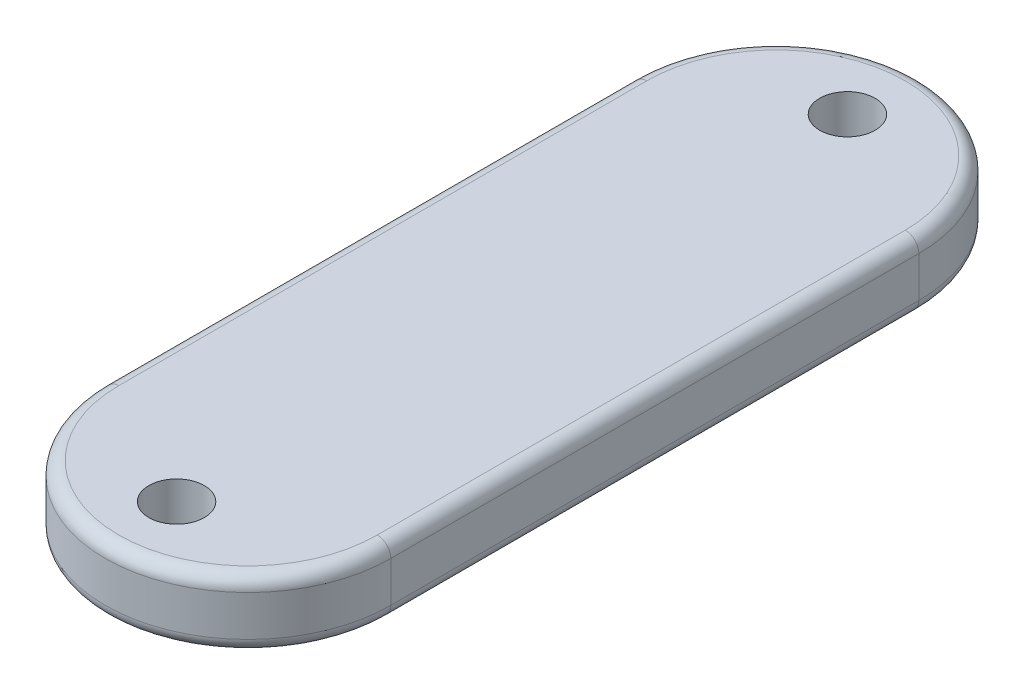
SolidWorks part; units mm, degrees
ref_plane "Plan de face" through (0, 0, 0) normal (0, 0, 1) x (1, 0, 0)
ref_plane "Plan de dessus" through (0, 0, 0) normal (0, 1, 0) x (1, 0, 0)
ref_plane "Plan de droite" through (0, 0, 0) normal (1, 0, 0) x (0, 0, -1)
sketch "Esquisse1" plane through (0, 0, 0) normal (0, 0, 1) x (1, 0, 0)
  line L0 (0, 4) -> (0, 14.517) construction
  line L1 (-2.95, 10.1031) -> (2.95, 10.1031)
  line L22 (2.95, 10.1031) -> (2.95, 8.4831)
  line L23 (2.95, 8.4831) -> (5.71, 8.4831)
  line L24 (5.71, 8.4831) -> (5.71, 6.9831)
  line L25 (5.71, 6.9831) -> (3.5, 4.84)
  line L26 (3.5, 4.84) -> (-3.5, 4.84)
  line L27 (-5.71, 6.9831) -> (-3.5, 4.84)
  line L28 (-5.71, 8.4831) -> (-5.71, 6.9831)
  line L29 (-2.95, 8.4831) -> (-5.71, 8.4831)
  line L30 (-2.95, 10.1031) -> (-2.95, 8.4831)
  point P10 (0, 4.84)
  point P14 (0, 10.1031)
  point P41 (0, 0)
  point P46 (0, 0)
  line B0 (0, 0) -> (0, 4) construction
  line B1 (0, 4) -> (0.866, 4.5)
  line B2 (0, 4) -> (-0.866, 4.5)
  line B3 (0.866, 4.5) -> (3.4393, 4.5)
  line B4 (3.4393, 4.5) -> (6, 7.0607)
  line B5 (6, 7.0607) -> (6, 8.5)
  line B6 (6, 8.5) -> (3, 8.5)
  line B7 (3, 8.5) -> (3, 9.5)
  line B8 (3, 9.5) -> (3.5, 9.5)
  line B9 (3.5, 9.5) -> (3.5, 10)
  line B10 (3.5, 10) -> (8.5, 10)
  line B11 (0, 0) -> (1.2745, 0) construction
  line B12 (-3.5, -10) -> (-8.5, -10)
  line B13 (-3.4393, -4.5) -> (-6, -7.0607)
  line B14 (-3.5, 9.5) -> (-3.5, 10)
  line B15 (-3, 9.5) -> (-3.5, 9.5)
  line B16 (-3, 8.5) -> (-3, 9.5)
  line B17 (-6, 8.5) -> (-3, 8.5)
  line B18 (-6, 7.0607) -> (-6, 8.5)
  line B19 (-0.866, 4.5) -> (-3.4393, 4.5)
  line B20 (-3.4393, 4.5) -> (-6, 7.0607)
  line B21 (-3.5, 10) -> (-8.5, 10)
  line B22 (-0.866, -4.5) -> (-3.4393, -4.5)
  line B23 (-6, -7.0607) -> (-6, -8.5)
  line B24 (-6, -8.5) -> (-3, -8.5)
  line B25 (-3, -8.5) -> (-3, -9.5)
  line B26 (-3, -9.5) -> (-3.5, -9.5)
  line B27 (-3.5, -9.5) -> (-3.5, -10)
  line B28 (3.5, -10) -> (8.5, -10)
  line B29 (3.5, -9.5) -> (3.5, -10)
  line B30 (3, -9.5) -> (3.5, -9.5)
  line B31 (3, -8.5) -> (3, -9.5)
  line B32 (6, -8.5) -> (3, -8.5)
  line B33 (6, -7.0607) -> (6, -8.5)
  line B34 (3.4393, -4.5) -> (6, -7.0607)
  line B35 (0.866, -4.5) -> (3.4393, -4.5)
  line B36 (0, -4) -> (-0.866, -4.5)
  line B37 (0, -4) -> (0.866, -4.5)
  line B38 (10, -3.5) -> (10, -8.5)
  line B39 (9.5, -3.5) -> (10, -3.5)
  line B40 (8.5, -3) -> (9.5, -3)
  line B41 (9.5, -3) -> (9.5, -3.5)
  line B42 (8.5, -6) -> (8.5, -3)
  line B43 (7.0607, -6) -> (8.5, -6)
  line B44 (4.5, -3.4393) -> (7.0607, -6)
  line B45 (4.5, -0.866) -> (4.5, -3.4393)
  line B46 (4.5, 0.866) -> (4.5, 3.4393)
  line B47 (4.5, 3.4393) -> (7.0607, 6)
  line B48 (7.0607, 6) -> (8.5, 6)
  line B49 (8.5, 6) -> (8.5, 3)
  line B50 (8.5, 3) -> (9.5, 3)
  line B51 (9.5, 3) -> (9.5, 3.5)
  line B52 (9.5, 3.5) -> (10, 3.5)
  line B53 (10, 3.5) -> (10, 8.5)
  line B54 (-3.5, -9.5) -> (-3.5, -10)
  line B55 (-3, -8.5) -> (-3, -9.5)
  line B56 (-3, -9.5) -> (-3.5, -9.5)
  line B57 (-6, -8.5) -> (-3, -8.5)
  line B58 (-6, -7.0607) -> (-6, -8.5)
  line B59 (-3.4393, -4.5) -> (-6, -7.0607)
  line B60 (-0.866, -4.5) -> (-3.4393, -4.5)
  line B61 (0.866, -4.5) -> (3.4393, -4.5)
  line B62 (3.4393, -4.5) -> (6, -7.0607)
  line B63 (6, -7.0607) -> (6, -8.5)
  line B64 (6, -8.5) -> (3, -8.5)
  line B65 (3, -8.5) -> (3, -9.5)
  line B66 (3, -9.5) -> (3.5, -9.5)
  line B67 (3.5, -9.5) -> (3.5, -10)
  line B68 (-10, 3.5) -> (-10, 8.5)
  line B69 (-9.5, 3.5) -> (-10, 3.5)
  line B70 (-8.5, 3) -> (-9.5, 3)
  line B71 (-9.5, 3) -> (-9.5, 3.5)
  line B72 (-8.5, 6) -> (-8.5, 3)
  line B73 (-7.0607, 6) -> (-8.5, 6)
  line B74 (-4.5, 3.4393) -> (-7.0607, 6)
  line B75 (-4.5, 0.866) -> (-4.5, 3.4393)
  line B76 (-4.5, -0.866) -> (-4.5, -3.4393)
  line B77 (-4.5, -3.4393) -> (-7.0607, -6)
  line B78 (-7.0607, -6) -> (-8.5, -6)
  line B79 (-8.5, -6) -> (-8.5, -3)
  line B80 (-8.5, -3) -> (-9.5, -3)
  line B81 (-9.5, -3) -> (-9.5, -3.5)
  line B82 (-9.5, -3.5) -> (-10, -3.5)
  line B83 (-10, -3.5) -> (-10, -8.5)
  line B84 (4, 0) -> (4.5, -0.866)
  line B85 (4, 0) -> (4.5, 0.866)
  line B86 (0, -4) -> (-0.866, -4.5)
  line B87 (0, -4) -> (0.866, -4.5)
  line B88 (-4, 0) -> (-4.5, 0.866)
  line B89 (-4, 0) -> (-4.5, -0.866)
  line B90 (0, 0) -> (1.9445, 1.9445) construction
  arc B91 (8.5, 10) -> (10, 8.5) centre (8.5, 8.5) cw
  arc B92 (-8.5, 10) -> (-10, 8.5) centre (-8.5, 8.5) ccw
  arc B93 (-8.5, -10) -> (-10, -8.5) centre (-8.5, -8.5) cw
  arc B94 (8.5, -10) -> (10, -8.5) centre (8.5, -8.5) ccw
  circle B95 centre (0, 0) radius 2.75
  dimension "D1" = 2.95
  dimension "D2" = 1.62
  dimension "D3" = 2.76
  dimension "D4" = 1.5
  dimension "D5" = 135.88
  dimension "D6" = 3.5
  dimension "D7" = 0.34
sketch_block_instance "Bloc1-1"
sketch_block "Bloc1"
extrude "Boss.-Extru.1" add sketch "Esquisse1" against normal blind 20 contours L0 L26 L25 L24 L23 L22 L1 | L26 L0 L1 L30 L29 L28 L27 region at (-2.3548, 7.3163, 0) region at (2.3548, 7.3163, 0)
fillet "Congé1" radius 0.5 10 edges at (0, 4.84, -20) (-4.605, 5.9116, -20) (-5.71, 7.7331, -20) (4.605, 5.9116, -20) (5.71, 7.7331, -20) (-5.71, 7.7331, 0) (-4.605, 5.9116, 0) (0, 4.84, 0) (4.605, 5.9116, 0) (5.71, 7.7331, 0)
fillet "Congé2" radius 1 6 edges at (5.5636, 7.0451, -0.1464) (5.5636, 7.0451, -19.8536) (-5.5636, 7.0451, -0.1464) (-5.5636, 7.0451, -19.8536) (-5.71, 6.9831, -10) (5.71, 6.9831, -10)
sketch "Esquisse3" plane through (0, 10.1031, 0) normal (0, 1, 0) x (1, 0, 0)
  line L0 (0, 0) -> (0, 20) construction
  line L1 (-2.95, 20) -> (2.95, 20) construction
  line L3 (-10.55, 29.5) -> (10.55, 29.5)
  line L4 (-10.55, 29.5) -> (-10.55, -9.5)
  line L5 (-10.55, -9.5) -> (10.55, -9.5)
  line L6 (10.55, 29.5) -> (10.55, -9.5)
  line L7 (-10.55, 29.5) -> (10.55, -9.5) construction
  line L8 (-10.55, -9.5) -> (10.55, 29.5) construction
  point P5 (0, 10)
  dimension "D1" = 21.1
  dimension "D2" = 39
extrude "Boss.-Extru.2" add sketch "Esquisse3" along normal blind 5
sketch "Esquisse5" plane through (0, 0, 0) normal (0, 0, 1) x (1, 0, 0)
  line L0 (-5.21, 8.4831) -> (-5.71, 8.4831) construction
  line L1 (-3.5, 4.84) -> (-5.4062, 6.6885) construction
  line L2 (3.5, 4.84) -> (-3.5, 4.84) construction
  line L3 (5.4062, 6.6885) -> (3.5, 4.84) construction
  line L4 (5.71, 8.4831) -> (5.71, 7.4064) construction
  line L5 (5.71, 8.4831) -> (5.21, 8.4831) construction
  line L6 (2.95, 8.4831) -> (5.21, 8.4831) construction
  line L7 (-2.95, 8.4831) -> (-5.21, 8.4831) construction
  line L8 (-5.71, 7.4064) -> (-5.71, 8.4831) construction
  line L9 (-5.21, 8.4831) -> (-5.71, 8.4831)
  line L10 (-3.5, 4.84) -> (-5.4062, 6.6885)
  line L11 (3.5, 4.84) -> (-3.5, 4.84)
  line L12 (5.4062, 6.6885) -> (3.5, 4.84)
  line L13 (5.71, 8.4831) -> (5.71, 7.4064)
  line L14 (5.71, 8.4831) -> (5.21, 8.4831)
  line L15 (2.95, 8.4831) -> (5.21, 8.4831)
  line L16 (-2.95, 8.4831) -> (-5.21, 8.4831)
  line L17 (-5.71, 7.4064) -> (-5.71, 8.4831)
  line L18 (-2.95, 8.4831) -> (2.95, 8.4831)
  arc A0 (5.4062, 6.6885) -> (5.71, 7.4064) centre (4.71, 7.4064) ccw construction
  arc A1 (-5.71, 7.4064) -> (-5.4062, 6.6885) centre (-4.71, 7.4064) ccw construction
  arc A2 (5.4062, 6.6885) -> (5.71, 7.4064) centre (4.71, 7.4064) ccw
  arc A3 (-5.71, 7.4064) -> (-5.4062, 6.6885) centre (-4.71, 7.4064) ccw
extrude "Enlèv. mat.-Extru.1" cut sketch "Esquisse5" against normal through all
sketch "Esquisse6" plane through (0, 15.1031, 0) normal (0, 1, 0) x (1, 0, 0)
  line L0 (10.55, 29.5) -> (-10.55, 29.5) construction
  line L1 (-10.55, -9.5) -> (10.55, -9.5) construction
  line L2 (0, 29.5) -> (0, 40.05) construction
  line L3 (0, -9.5) -> (0, -20.05) construction
  arc A0 (-10.55, 29.5) -> (10.55, 29.5) centre (0, 29.5) cw
  arc A1 (-10.55, -9.5) -> (10.55, -9.5) centre (0, -9.5) ccw
  circle A2 centre (0, -14.775) radius 2.05
  circle A3 centre (0, 34.775) radius 2.05
  line M3 (10.55, 29.5) -> (-10.55, 29.5)
  line M5 (-10.55, -9.5) -> (10.55, -9.5)
  dimension "D1" = 4.1
  dimension "D2" = 4.1
extrude "Boss.-Extru.3" add sketch "Esquisse6" against normal blind 5 contours A0 A3 M3 | A1 A2 M5 region at (0, 15.1031, -39.8141) region at (0, 15.1031, 9.7359)
fillet "Congé4" radius 1 8 edges at (0, 10.1031, -40.05) (-10.55, 10.1031, -10) (0, 10.1031, 20.05) (10.55, 10.1031, -10) (-10.55, 15.1031, -10) (0, 15.1031, -40.05) (10.55, 15.1031, -10) (0, 15.1031, 20.05)
